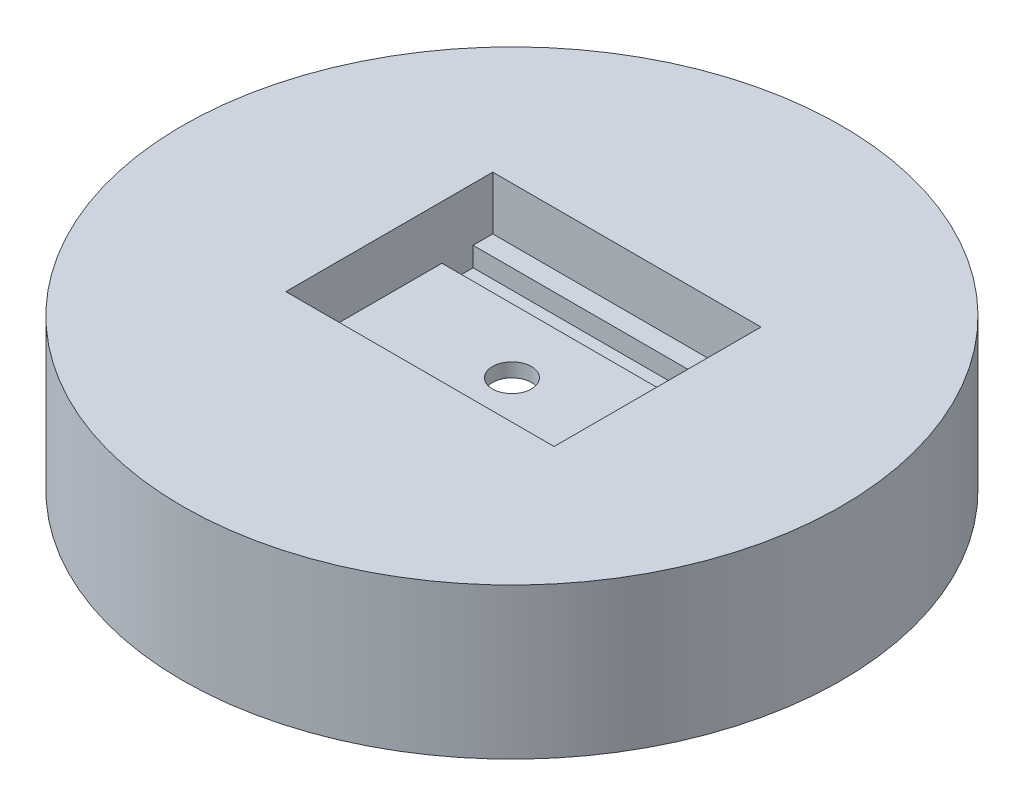
SolidWorks part; units mm, degrees
ref_plane "Front Plane" through (0, 0, 0) normal (0, 0, 1) x (1, 0, 0)
ref_plane "Top Plane" through (0, 0, 0) normal (0, 1, 0) x (1, 0, 0)
ref_plane "Right Plane" through (0, 0, 0) normal (1, 0, 0) x (0, 0, -1)
sketch "Sketch3" plane through (0, 0, 0) normal (0, 0, 1) x (1, 0, 0)
  line L0 (0, 0) -> (17.5, 0) construction
  line L2 (17.5, 0) -> (1.27, 5.4429)
  line L3 (1.27, -13.9932) -> (1.27, 1.2597) construction
  line L4 (0, 0) -> (0, -13.9932) construction
  line L5 (17.5, 0) -> (21.5, 0)
  line L6 (1.27, 9.8395) -> (1.27, 5.4429)
  line L9 (21.5, 9.8395) -> (21.5, 0)
  line L11 (21.5, 9.8395) -> (1.27, 9.8395)
  line L12 (1.27, 5.4429) -> (1.27, 9.8395) construction
  dimension "D1" = 17.5
  dimension "D3" = 1.27
  dimension "D4" = 4
revolve "Revolve1" add sketch "Sketch3" angle 360 about L4
sketch "Sketch for side slot DNU" plane through (0, 0, 0) normal (0, 0, 1) x (1, 0, 0)
  line L0 (0, 0) -> (0, 18.8028) construction
  line L1 (0, 0) -> (-24.5114, 0) construction
  line L2 (-7.874, 8.382) -> (7.874, 8.382)
  line L3 (-7.874, 8.382) -> (-7.874, 9.398)
  line L4 (-7.874, 9.398) -> (7.874, 9.398)
  line L5 (7.874, 8.382) -> (7.874, 9.398)
  line L6 (-7.874, 8.382) -> (7.874, 9.398) construction
  line L7 (-7.874, 9.398) -> (7.874, 8.382) construction
  point P3 (0, 8.89)
  dimension "D1" = 15.748
  dimension "D2" = 1.016
  dimension "D3" = 8.89
ref_plane "Plane for board depression" through (0, 12.7, 0) normal (0, 1, 0) x (1, 0, 0)
sketch "Sketch5" plane through (0, 12.7, 0) normal (0, 1, 0) x (1, 0, 0)
  line L0 (0, 0) -> (35.335, 0) construction
  line L1 (0, 0) -> (0, 26.2568) construction
  line L2 (8.75, 7.5) -> (-8.75, 7.5)
  line L3 (-8.75, 7.5) -> (-8.75, -6)
  line L4 (-8.75, -6) -> (8.75, -6)
  line L5 (8.75, -6) -> (8.75, 7.5)
  point P7 (0, 7.5)
  dimension "D1" = 17.5
  dimension "D2" = 13.5
  dimension "D3" = 7.5
extrude "Cut-Extrude1" cut sketch "Sketch5" against normal blind 6.35
ref_plane "plane for header solder depression" through (0, 15.24, 0) normal (0, 1, 0) x (1, 0, 0)
sketch "Sketch6" plane through (0, 15.24, 0) normal (0, 1, 0) x (1, 0, 0)
  line L0 (0, 0) -> (0, 25.5996) construction
  line L1 (0, 0) -> (0, 26.2568) construction
  line L2 (31.19, 5.2) -> (-31.19, 5.2) construction
  line L3 (8.75, 7.5) -> (-8.75, 7.5) construction
  line L4 (8.75, 6.216) -> (-8.75, 6.216)
  line L5 (8.75, 4.184) -> (-8.75, 4.184)
  line L6 (-8.75, 6.216) -> (-8.75, 4.184)
  line L8 (8.75, 6.216) -> (8.75, 4.184)
  line L10 (31.19, 6.216) -> (-31.19, 6.216) construction
  line L11 (31.19, 4.184) -> (-31.19, 4.184) construction
  point P9 (0, 5.2)
  dimension "D1" = 2.3
  dimension "D2" = 1.016
  dimension "D3" = 1.016
extrude "Cut-Extrude2" cut sketch "Sketch6" against normal blind 10.16
